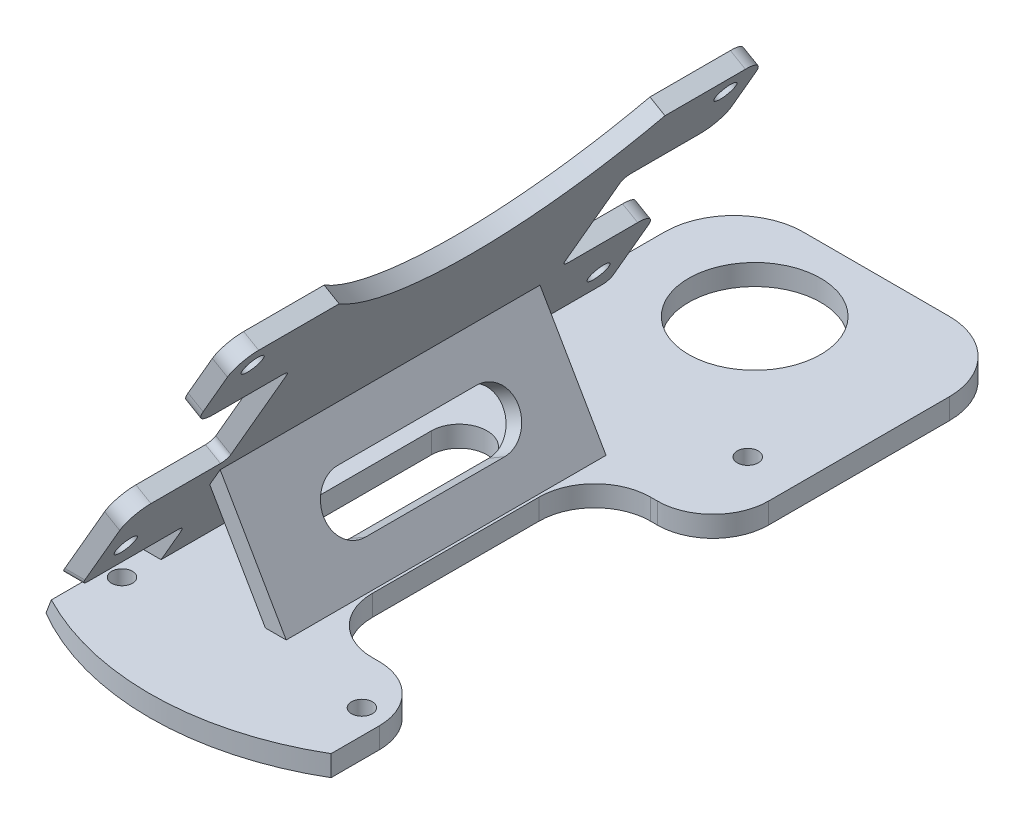
SolidWorks part; units mm, degrees
material "聚脂树脂"
ref_plane "前视基准面" through (0, 0, 0) normal (0, 0, 1) x (1, 0, 0)
ref_plane "上视基准面" through (0, 0, 0) normal (0, 1, 0) x (1, 0, 0)
ref_plane "右视基准面" through (0, 0, 0) normal (1, 0, 0) x (0, 0, -1)
other "Configuration Table"
sketch "草图2" plane through (0, 0, 0) normal (0, 0, 1) x (1, 0, 0)
  line L0 (0, 0) -> (0, 88.747) construction
  line L1 (0, 0) -> (110.2523, 0) construction
  line L2 (0, 0) -> (28.5, 49.3634)
  line L3 (28.5, 49.3634) -> (30.6651, 48.1134)
  line L4 (30.6651, 48.1134) -> (4.6188, 3)
  line L5 (4.6188, 3) -> (41, 3)
  line L6 (41, 3) -> (41, 0)
  line L7 (41, 0) -> (0, 0)
  dimension "D1" = 60
  dimension "D2" = 3
  dimension "D3" = 2.5
  dimension "D4" = 41
  dimension "D5" = 57
extrude "凸台-拉伸1" add sketch "草图2" along normal blind 38 and the other way blind 38
sketch "草图3" plane through (0, 0, 38) normal (0, 0, 1) x (1, 0, 0)
  line L0 (0, 0) -> (0, 52.6153) construction
  line L1 (0, 0) -> (59.4187, 0) construction
  line L2 (12.6188, 16.8564) -> (14.1188, 19.4545)
  line L3 (4.6188, 3) -> (30.6651, 48.1134) construction
  line L4 (14.1188, 19.4545) -> (23.6188, 3)
  line L5 (41, 3) -> (4.6188, 3) construction
  line L6 (23.6188, 3) -> (20.6188, 3)
  line L7 (20.6188, 3) -> (12.6188, 16.8564)
  dimension "D1" = 3
  dimension "D2" = 3
  dimension "D3" = 16
extrude "凸台-拉伸2" add sketch "草图3" against normal blind 60
sketch "草图4" plane through (0, 0, 0) normal (-0.866, 0.5, 0) x (0, 0, 1)
  line L0 (0, 0) -> (0, 67.8979) construction
  line L1 (0, 0) -> (54.9113, 0) construction
  line L2 (0, 35) -> (62.8022, 35) construction
  line L3 (38, 26) -> (38, 44)
  line L4 (38, 57) -> (38, 0) construction
  line L5 (38, 44) -> (24, 44)
  line L6 (24, 44) -> (24, 26)
  line L7 (38, 26) -> (24, 26)
  line L8 (-38, 26) -> (-24, 26)
  line L9 (-24, 44) -> (-24, 26)
  line L10 (-38, 44) -> (-24, 44)
  line L11 (-38, 26) -> (-38, 44)
  circle A0 centre (34, 53.25) radius 1.5
  circle A1 centre (34, 16.75) radius 1.5
  circle A2 centre (-34, 16.75) radius 1.5
  circle A3 centre (-34, 53.25) radius 1.5
  point P21 (38, 35)
  point P22 (24, 35)
  dimension "D1" = 3
  dimension "D2" = 68
  dimension "D3" = 36.5
  dimension "D4" = 35
  dimension "D5" = 9
  dimension "D6" = 14
extrude "切除-拉伸1" cut sketch "草图4" against normal blind 6
sketch "草图6" plane through (0, 0, 38) normal (0, 0, 1) x (1, 0, 0)
  line L7 (23.6188, 3) -> (14.1188, 19.4545) construction
  line L8 (12.6188, 16.8564) -> (20.6188, 3) construction
  line L9 (23.6188, 3) -> (14.1188, 19.4545)
  line L10 (12.6188, 16.8564) -> (20.6188, 3)
  line L11 (14.1188, 19.4545) -> (12.6188, 16.8564)
  line L12 (20.6188, 3) -> (23.6188, 3)
extrude "切除-拉伸3" cut sketch "草图6" against normal blind 14
fillet "圆角2" radius 3 6 edges at (29.5825, 48.7384, -38) (23.0825, 37.4801, -38) (29.5825, 48.7384, 38) (23.0825, 37.4801, 38) (14.0825, 21.8917, 38) (14.0825, 21.8917, -38)
sketch "草图9" plane through (0, 0, 0) normal (0, -1, 0) x (1, 0, 0)
  line L0 (0, 0) -> (73.7033, 0) construction
  line L1 (13, -12.5) -> (13, 12.5) construction
  line L4 (9, -12.5) -> (9, 12.5)
  line L5 (17, -12.5) -> (17, 12.5)
  line L6 (0, -38) -> (0, 38) construction
  arc A2 (9, -12.5) -> (17, -12.5) centre (13, -12.5) ccw
  arc A3 (17, 12.5) -> (9, 12.5) centre (13, 12.5) ccw
  circle A4 centre (13, 30) radius 1.5
  circle A5 centre (13, -30) radius 1.5
  point P5 (13, 0)
  dimension "D2" = 4
  dimension "D4" = 3
  dimension "D6" = 60
  dimension "D1" = 25
  dimension "D3" = 13
  dimension "D5" = 13
sketch "草图11" plane through (19.0131, 10.9772, 0) normal (0.866, 0.5, 0) x (0, 0, -1)
  line L0 (-10, 0) -> (10, 0) construction
  line L1 (-10, 4) -> (10, 4)
  line L2 (-10, -4) -> (10, -4)
  arc A0 (-10, 4) -> (-10, -4) centre (-10, 0) ccw
  arc A1 (10, -4) -> (10, 4) centre (10, 0) ccw
  point P2 (0, 0)
  dimension "D2" = 4
  dimension "D1" = 20
extrude "切除-拉伸6" cut sketch "草图11" against normal blind 3
sketch "草图13" plane through (0, 3, 0) normal (0, 1, 0) x (1, 0, 0)
  line L0 (41, 38) -> (41, -38) construction
  line L1 (41, -38) -> (4.6188, -38) construction
  circle A0 centre (37.5, -27) radius 1.5
  circle A1 centre (4, -28) radius 1.5
  circle A2 centre (34, 32) radius 1.5
  circle A3 centre (4, 32) radius 1.5
  dimension "D1" = 3
  dimension "D2" = 3
  dimension "D3" = 3
  dimension "D4" = 3
  dimension "D5" = 3.5
  dimension "D6" = 11
  dimension "D7" = 10
  dimension "D8" = 37
  dimension "D9" = 37
  dimension "D11" = 70
  dimension "D10" = 70
  dimension "D12" = 7
extrude "切除-拉伸7" cut sketch "草图13" against normal blind 10
sketch "草图15" plane through (0, 0, 38) normal (0, 0, 1) x (1, 0, 0)
  line L0 (4.6188, 3) -> (1.7321, 3)
  line L1 (11.5, 19.9186) -> (0, 0) construction
  line L2 (1.7321, 3) -> (5.1962, 9)
  line L3 (5.1962, 9) -> (8.0829, 9)
  line L4 (4.6188, 3) -> (13.6651, 18.6686) construction
  line L5 (8.0829, 9) -> (4.6188, 3)
  dimension "D1" = 6
extrude "切除-拉伸9" cut sketch "草图15" against normal blind 15
mirror "镜向1" about plane through (0, 0, 0) normal (0, 0, 1) of "切除-拉伸9"
sketch "草图17" plane through (0, 3, 0) normal (0, 1, 0) x (1, 0, 0)
  line L0 (41, 38) -> (0, 38)
  line L1 (0, 38) -> (0, 64)
  line L2 (0, 64) -> (41, 64)
  line L3 (41, 64) -> (41, 38)
  line L4 (0, 50) -> (41, 50) construction
  line L9 (0, -38) -> (41, -38)
  line L10 (41, -38) -> (41, -64)
  line L11 (41, -64) -> (0, -64)
  line L12 (0, -64) -> (0, -38)
  line L13 (5.9225, -50) -> (30.9787, -50) construction
  line L14 (20, -50) -> (20, -32.3657) construction
  line L15 (0, 38) -> (0, -38) construction
  line L16 (17, 50) -> (17, 71.806) construction
  circle A5 centre (17, 50) radius 9.5
  circle A6 centre (5, -45) radius 1.5
  circle A7 centre (5, -55) radius 1.5
  circle A8 centre (35, -55) radius 1.5
  circle A9 centre (35, -45) radius 1.5
  circle A10 centre (20, -50) radius 9.5
  dimension "D2" = 17
  dimension "D3" = 26
  dimension "D4" = 3
  dimension "D6" = 10
  dimension "D9" = 19
  dimension "D10" = 20
  dimension "D11" = 19
  dimension "D1" = 26
  dimension "D5" = 15
  dimension "D7" = 50
  dimension "D8" = 12
extrude "凸台-拉伸3" add sketch "草图17" against normal blind 3
fillet "圆角3" radius 10 4 edges at (41, 1.5, -64) (0, 1.5, -64) (41, 1.5, 64) (0, 1.5, 64)
sketch "草图18" plane through (0, 3, 0) normal (0, 1, 0) x (1, 0, 0)
  line L0 (0, 0) -> (102.439, 0) construction
  line L1 (41, 20) -> (24, 20)
  line L2 (41, 54) -> (41, -54) construction
  line L3 (24, 20) -> (24, -20)
  line L4 (41, 20) -> (41, -20)
  line L5 (41, -20) -> (24, -20)
  line L6 (12, -12.5) -> (12, 12.5) construction
  line L7 (8, -12.5) -> (8, 12.5)
  line L8 (16, -12.5) -> (16, 12.5)
  line L9 (0, 38) -> (0, -38) construction
  arc A0 (8, -12.5) -> (16, -12.5) centre (12, -12.5) ccw
  arc A1 (16, 12.5) -> (8, 12.5) centre (12, 12.5) ccw
  point P10 (41, 0)
  point P11 (24, 0)
  point P13 (12, 0)
  dimension "D4" = 4
  dimension "D1" = 17
  dimension "D2" = 20
  dimension "D3" = 25
  dimension "D5" = 12
extrude "切除-拉伸10" cut sketch "草图18" against normal blind 10
fillet "圆角4" radius 8 4 edges at (41, 1.5, -20) (24, 1.5, -20) (24, 1.5, 20) (41, 1.5, 20)
sketch "草图21" plane through (0, 0, 0) normal (-0.866, 0.5, 0) x (0, 0, 1)
  line L0 (0, 0) -> (0, 68.7823) construction
  line L6 (-35, 57) -> (35, 57) construction
  line L7 (-23.4307, 57) -> (23.4307, 57)
  line L8 (-8, 15) -> (8, 15) construction
  line L9 (-8, 19) -> (8, 19)
  line L10 (-8, 11) -> (8, 11)
  line L11 (-38, 0) -> (38, 0) construction
  arc A0 (-23.4307, 57) -> (23.4307, 57) centre (0, 83) ccw
  arc A1 (-8, 19) -> (-8, 11) centre (-8, 15) ccw
  arc A2 (8, 11) -> (8, 19) centre (8, 15) ccw
  point P10 (0, 15)
  dimension "D1" = 35
  dimension "D4" = 4
  dimension "D2" = 26
  dimension "D3" = 16
  dimension "D5" = 15
extrude "切除-拉伸11" cut sketch "草图21" against normal blind 4
fillet "圆角5" radius 1 8 edges at (6.6395, 9, -23) (6.6395, 9, 23) (14.0825, 21.8917, 24) (23.0825, 37.4801, 24) (14.0825, 21.8917, -24) (23.0825, 37.4801, -24) (6.6395, 9, 38) (6.6395, 9, -38)
sketch "草图22" plane through (0, 3, 0) normal (0, 1, 0) x (1, 0, 0)
  line L0 (0, 0) -> (82.6376, 0) construction
  line L1 (41, -28) -> (41, -54) construction
  line L2 (0, 38) -> (0, -38) construction
  line L3 (0, -34.9314) -> (0, -65.9767)
  line L4 (0, -65.9767) -> (41, -65.9767)
  line L5 (41, -65.9767) -> (41, -34.9314)
  arc A0 (0, -34.9314) -> (41, -34.9314) centre (20.5, 0) ccw
  circle A1 centre (20, -50) radius 9.5 construction
  dimension "D2" = 31.0453
  dimension "D1" = 20.5
extrude "切除-拉伸12" cut sketch "草图22" against normal blind 10
